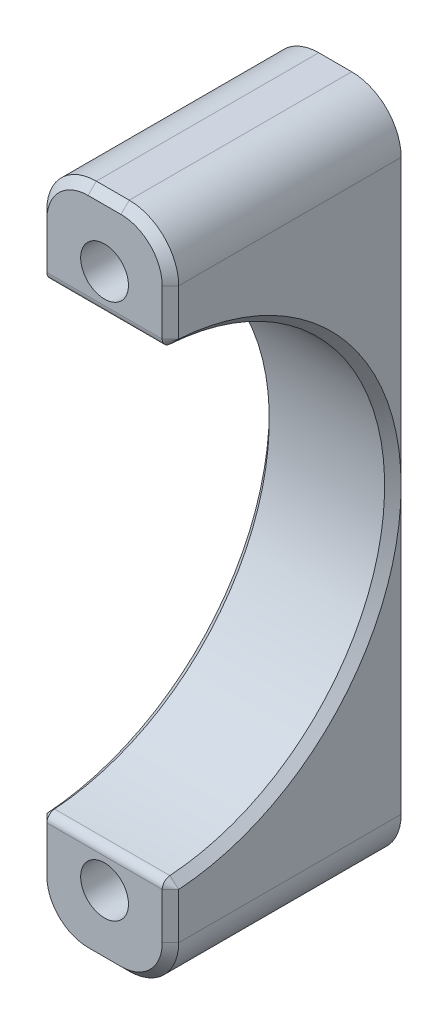
SolidWorks part; units mm, degrees
material "尼龙 101"
ref_plane "前视基准面" through (0, 0, 0) normal (0, 0, 1) x (1, 0, 0)
ref_plane "上视基准面" through (0, 0, 0) normal (0, 1, 0) x (1, 0, 0)
ref_plane "右视基准面" through (0, 0, 0) normal (1, 0, 0) x (0, 0, -1)
sketch "草图1" plane through (0, 0, 0) normal (0, 0, 1) x (1, 0, 0)
  line L0 (152.2649, 16.264) -> (152.2649, -16.264) construction
  line L1 (151.2649, 20.264) -> (153.2649, 20.264)
  line L2 (148.2649, 17.264) -> (148.2649, -17.264)
  line L3 (151.2649, -20.264) -> (153.2649, -20.264)
  line L4 (156.2649, 17.264) -> (156.2649, -17.264)
  line L5 (148.2649, 20.264) -> (156.2649, -20.264) construction
  line L6 (148.2649, -20.264) -> (156.2649, 20.264) construction
  circle A0 centre (152.2649, 16.264) radius 1.45
  circle A1 centre (152.2649, -16.264) radius 1.45
  arc A2 (153.2649, -20.264) -> (156.2649, -17.264) centre (153.2649, -17.264) ccw
  arc A3 (148.2649, -17.264) -> (151.2649, -20.264) centre (151.2649, -17.264) ccw
  arc A4 (153.2649, 20.264) -> (156.2649, 17.264) centre (153.2649, 17.264) cw
  arc A5 (151.2649, 20.264) -> (148.2649, 17.264) centre (151.2649, 17.264) ccw
  point P0 (152.2649, 0)
  dimension "D3" = 2.9
  dimension "D4" = 3
  dimension "D1" = 8
  dimension "D2" = 4
extrude "凸台-拉伸1" add sketch "草图1" along normal blind 14
sketch "草图2" plane through (148.2649, 0, 0) normal (-1, 0, 0) x (0, 0, 1)
  line L0 (0, 0) -> (14.5, 0) construction
  circle A0 centre (14.5, 0) radius 14
  dimension "D2" = 28
  dimension "D1" = 14.5
extrude "切除-拉伸1" cut sketch "草图2" against normal through all both and the other way through all
fillet "圆角1" radius 0.5 2 edges at (152.2649, -13.9911, 14) (152.2649, 13.9911, 14)
chamfer "倒角1" distance 0.5 angle 45 16 edges at (156.2649, 0, 0.5) (156.2649, -14.1243, 13.8655) (156.2649, 14.1243, 13.8655) (156.2649, -15.8648, 14) (156.2649, 15.8648, 14) (155.3862, -19.3854, 14) (155.3862, 19.3854, 14) (152.2649, -20.264, 14) (152.2649, 20.264, 14) (149.1436, -19.3854, 14) (149.1436, 19.3854, 14) (148.2649, -15.8648, 14) (148.2649, 15.8648, 14) (148.2649, -14.1243, 13.8655) (148.2649, 14.1243, 13.8655) (148.2649, 0, 0.5)
